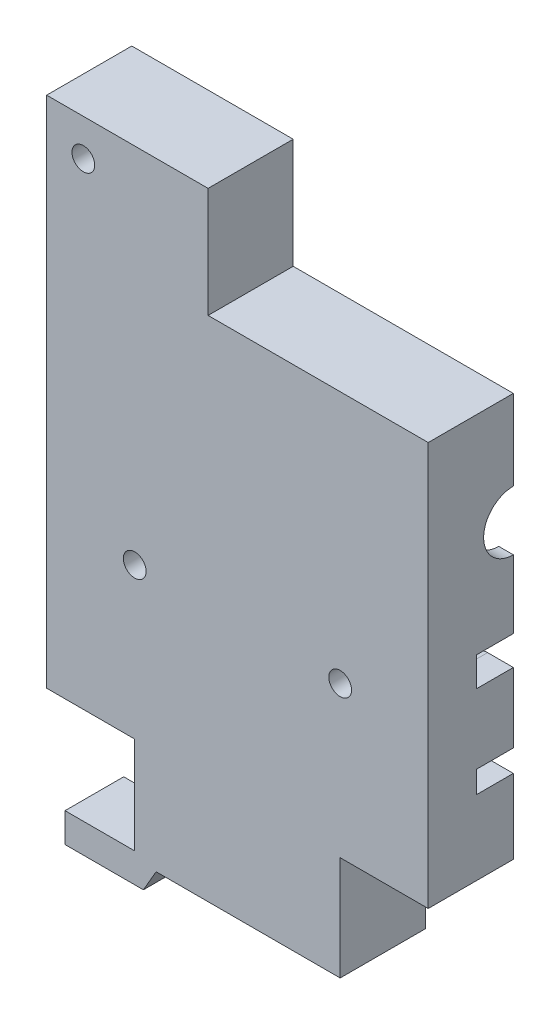
SolidWorks part; units mm, degrees
ref_plane "Alzado" through (0, 0, 0) normal (0, 0, 1) x (1, 0, 0)
ref_plane "Planta" through (0, 0, 0) normal (0, 1, 0) x (1, 0, 0)
ref_plane "Vista lateral" through (0, 0, 0) normal (1, 0, 0) x (0, 0, -1)
sketch "Croquis1" plane through (0, 0, 0) normal (0, 0, 1) x (1, 0, 0)
  line L0 (0, 0) -> (0, 90)
  line L1 (0, 90) -> (52, 90)
  line L2 (52, 90) -> (52, 0)
  line L3 (52, 0) -> (0, 0)
  dimension "D1" = 90
  dimension "D2" = 52
extrude "Saliente-Extruir1" add sketch "Croquis1" along normal blind 11.6
ref_plane "Plano1" through (50, 0, 0) normal (1, 0, 0) x (0, 0, -1)
sketch "Croquis2" plane through (50, 0, 0) normal (1, 0, 0) x (0, 0, -1)
  line L0 (0, 0) -> (0, 90) construction
  line L1 (0, 52.45) -> (0, 67.55)
  arc A0 (0, 67.55) -> (0, 52.45) centre (0, 60) ccw
  dimension "D1" = 15.1
  dimension "D2" = 30
extrude "Cortar-Extruir1" cut sketch "Croquis2" against normal blind 48
ref_plane "Plano2" through (38, 0, 0) normal (1, 0, 0) x (0, 0, -1)
sketch "Croquis3" plane through (38, 0, 0) normal (1, 0, 0) x (0, 0, -1)
  line L0 (0, 0) -> (0, 90) construction
  line L1 (0, 7.45) -> (0, 22.55)
  line L2 (-11.6, 90) -> (0, 90) construction
  arc A0 (0, 22.55) -> (0, 7.45) centre (0, 15) ccw
  dimension "D1" = 15.1
  dimension "D2" = 75
extrude "Cortar-Extruir2" cut sketch "Croquis3" against normal blind 24
sketch "Croquis4" plane through (52, 0, 0) normal (1, 0, 0) x (0, 0, -1)
  line L0 (0, 0) -> (0, 90) construction
  line L1 (0, 0) -> (0, 90)
  circle A0 centre (0, 60) radius 4.05
  dimension "D1" = 8.1
  dimension "D2" = 30
extrude "Cortar-Extruir3" cut sketch "Croquis4" against normal through all contours L1 A0 region at (52, 60, 1.7189)
sketch "Croquis5" plane through (52, 0, 0) normal (1, 0, 0) x (0, 0, -1)
  line L0 (0, 0) -> (0, 55.95) construction
  line L1 (0, 0) -> (0, 55.95)
  circle A0 centre (0, 15) radius 4.05
  dimension "D1" = 8.1
  dimension "D2" = 75
extrude "Cortar-Extruir4" cut sketch "Croquis5" against normal through all contours L1 A0 region at (52, 15, 1.7189)
sketch "Croquis6" plane through (0, 0, 0) normal (0, 0, -1) x (-1, 0, 0)
  line L10 (-2, 52.45) -> (-50, 52.45) construction
  line L13 (-2, 52.45) -> (-50, 52.45) construction
  line L18 (-2, 21.55) -> (-11.5, 21.55)
  line L19 (-11.5, 21.55) -> (-11.5, 25.05)
  line L20 (-11.5, 25.05) -> (-40.5, 25.05)
  line L21 (-2, 52.45) -> (-26, 52.45)
  line L22 (-40.5, 21.55) -> (-40.5, 25.05)
  line L23 (-40.5, 21.55) -> (-50, 21.55)
  line L24 (-26, 49.95) -> (-26, 22.55) construction
  line L25 (-2, 49.95) -> (-50, 49.95)
  line L26 (-50, 49.95) -> (-50, 21.55)
  line L27 (-2, 49.95) -> (-2, 21.55)
  line L28 (-52, 45.95) -> (-52, 48.45)
  point P1 (-6.75, 21.55)
  dimension "D2" = 9.5
  dimension "D3" = 2.5
  dimension "D4" = 9.5
  dimension "D5" = 24.9
  dimension "D6" = 28.4
  dimension "D7" = 9.5
  dimension "D8" = 3.5
  dimension "D9" = 3.5
  dimension "D10" = 9.5
extrude "Cortar-Extruir7" cut sketch "Croquis6" against normal blind 8 contours L27 L25 L26 L23 L22 L20 L19 L18 region at (26, 36.7516, 0)
sketch "Croquis7" plane through (0, 0, 8) normal (0, 0, -1) x (-1, 0, 0)
  line L0 (-2, 49.95) -> (-50, 49.95) construction
  line L3 (-50, 49.95) -> (-50, 21.55) construction
  circle A0 centre (-40, 40.55) radius 4
  dimension "D1" = 8
  dimension "D2" = 9.4
  dimension "D3" = 10
extrude "Saliente-Extruir2" add sketch "Croquis7" along normal blind 12
sketch "Croquis8" plane through (0, 0, 0) normal (0, 0, -1) x (-1, 0, 0)
  line L0 (-50, 49.95) -> (-50, 21.55) construction
  line L1 (-52, 19.05) -> (-52, 55.95) construction
  line L2 (-50, 46.65) -> (-50, 42.65)
  line L3 (-52, 42.65) -> (-52, 46.65)
  line L4 (-52, 46.65) -> (-50, 46.65)
  line L5 (-52, 42.65) -> (-50, 42.65)
  dimension "D1" = 4
  dimension "D2" = 3.3
extrude "Cortar-Extruir8" cut sketch "Croquis8" against normal blind 5
sketch "Croquis9" plane through (0, 0, 0) normal (0, 0, -1) x (-1, 0, 0)
  line L0 (-52, 42.65) -> (-48.4953, 42.65)
  line L1 (-46.4953, 40.65) -> (-46.4953, 37.65)
  line L2 (-46.4953, 37.65) -> (-52, 37.65)
  line L3 (-52, 19.05) -> (-52, 42.65) construction
  line L4 (-52, 37.65) -> (-52, 42.65)
  arc A0 (-46.4953, 40.65) -> (-48.4953, 42.65) centre (-48.4953, 40.65) ccw
  point P9 (-46.4953, 42.65)
  dimension "D3" = 2
  dimension "D1" = 5.5047
  dimension "D2" = 5
extrude "Saliente-Extruir4" add sketch "Croquis9" against normal blind 8
sketch "Croquis10" plane through (0, 0, -4) normal (0, 0, -1) x (-1, 0, 0)
  circle A0 centre (-40, 40.55) radius 4 construction
  circle A1 centre (-40, 40.55) radius 4
  circle A2 centre (-40, 40.55) radius 1.55
  dimension "D1" = 3.1
extrude "Cortar-Extruir9" cut sketch "Croquis10" against normal through all contours A2 region at (40, 40.55, -4)
sketch "Croquis11" plane through (0, 0, -4) normal (0, 0, -1) x (-1, 0, 0)
  circle A0 centre (-40, 40.55) radius 1.55 construction
  circle A1 centre (-40, 40.55) radius 1.55
  circle A2 centre (-40, 40.55) radius 2.8
  dimension "D1" = 5.6
extrude "Cortar-Extruir10" cut sketch "Croquis11" against normal blind 3
sketch "Croquis12" plane through (52, 0, 0) normal (1, 0, 0) x (0, 0, -1)
  line L0 (0, 19.05) -> (0, 42.65) construction
  line L1 (0, 30.15) -> (0, 33.15)
  line L2 (0, 33.15) -> (-5, 33.15)
  line L3 (-5, 33.15) -> (-5, 30.15)
  line L4 (-5, 30.15) -> (0, 30.15)
  dimension "D1" = 5
  dimension "D2" = 3
  dimension "D3" = 13.5
extrude "Cortar-Extruir11" cut sketch "Croquis12" against normal through all
sketch "Croquis13" plane through (0, 0, 0) normal (0, 0, -1) x (-1, 0, 0)
  line L0 (-52, 90) -> (-52, 75)
  line L2 (-52, 75) -> (-22, 75)
  line L3 (-22, 75) -> (-22, 90)
  line L4 (-52, 90) -> (0, 90) construction
  line L5 (-22, 90) -> (-52, 90)
  dimension "D1" = 30
  dimension "D2" = 15
extrude "Cortar-Extruir12" cut sketch "Croquis13" against normal blind 12
sketch "Croquis14" plane through (0, 0, 0) normal (0, 0, -1) x (-1, 0, 0)
  line L0 (-22, 90) -> (0, 90) construction
  line L1 (0, 90) -> (0, 64.05) construction
  circle A0 centre (-5, 85) radius 1.55
  circle A1 centre (-5, 85) radius 2.8
  dimension "D1" = 3.1
  dimension "D2" = 5.6
  dimension "D3" = 5
  dimension "D4" = 5
extrude "Cortar-Extruir13" cut sketch "Croquis14" against normal blind 12 contours A0 region at (5, 85, 0)
extrude "Cortar-Extruir14" cut sketch "Croquis14<3>" against normal blind 3
sketch "Croquis14<3>" plane through (0, 0, 0) normal (0, 0, -1) x (-1, 0, 0) same geometry as "Croquis14"
sketch "Croquis15" plane through (0, 0, 8) normal (0, 0, -1) x (-1, 0, 0)
  line L0 (-50, 30.15) -> (-2, 30.15)
  line L1 (-2, 30.15) -> (-2, 28.95)
  line L2 (-2, 30.15) -> (-2, 21.55) construction
  line L3 (-2, 28.95) -> (-50, 28.95)
  line L4 (-50, 30.15) -> (-50, 21.55) construction
  line L5 (-50, 28.95) -> (-50, 30.15)
  dimension "D1" = 1.2
extrude "Saliente-Extruir5" add sketch "Croquis15" along normal blind 8
sketch "Croquis16" plane through (0, 0, 0) normal (0, 0, -1) x (-1, 0, 0)
  line L0 (-52, 20) -> (-52, 0)
  line L2 (-52, 0) -> (-40, 0)
  line L3 (0, 0) -> (-52, 0) construction
  line L4 (-40, 0) -> (-40, 20)
  line L5 (-40, 20) -> (-52, 20)
  dimension "D1" = 20
  dimension "D2" = 12
extrude "Cortar-Extruir15" cut sketch "Croquis16" against normal through all
sketch "Croquis17" plane through (0, 0, 0) normal (0, 0, -1) x (-1, 0, 0)
  line L0 (0, 20) -> (-12, 20)
  line L1 (-12, 20) -> (-12, 0)
  line L2 (0, 0) -> (-40, 0) construction
  line L3 (-12, 0) -> (0, 0)
  line L4 (0, 0) -> (0, 20)
  dimension "D1" = 12
  dimension "D2" = 20
  dimension "D3" = 10.15
extrude "Cortar-Extruir16" cut sketch "Croquis17" against normal through all
sketch "Croquis18" plane through (0, 0, 11.6) normal (0, 0, 1) x (1, 0, 0)
  line L0 (2.5, 2.8) -> (12, 2.8)
  line L2 (2.5, 2.8) -> (2.5, 6.8)
  line L3 (2.5, 6.8) -> (12, 6.8)
  line L4 (12, 20) -> (12, 0) construction
  line L5 (12, 6.8) -> (12, 2.8)
  dimension "D1" = 4
  dimension "D2" = 2.8
  dimension "D3" = 9.5
extrude "Saliente-Extruir6" add sketch "Croquis18" against normal blind 8
sketch "Croquis19" plane through (0, 0, 8) normal (0, 0, -1) x (-1, 0, 0)
  line L0 (-2, 49.95) -> (-2, 33.15) construction
  line L1 (-2, 49.95) -> (-50, 49.95) construction
  circle A0 centre (-12, 40.55) radius 4
  dimension "D1" = 8
  dimension "D2" = 10
  dimension "D3" = 9.4
extrude "Saliente-Extruir7" add sketch "Croquis19" along normal up to surface (12 mm away) up to face at (37.2, 40.55, -4)
sketch "Croquis20" plane through (0, 0, -4) normal (0, 0, -1) x (-1, 0, 0)
  circle A0 centre (-12, 40.55) radius 4 construction
  circle A1 centre (-12, 40.55) radius 4
  circle A2 centre (-12, 40.55) radius 1.55
  circle A3 centre (-12, 40.55) radius 2.8
  dimension "D1" = 3.1
  dimension "D2" = 5.6
extrude "Cortar-Extruir17" cut sketch "Croquis20" against normal through all contours A2 region at (12, 40.55, -4)
extrude "Cortar-Extruir18" cut sketch "Croquis20<3>" against normal blind 3 contours A3 A2 region at (14.7208, 40.55, -4)
sketch "Croquis20<3>" plane through (0, 0, -4) normal (0, 0, -1) x (-1, 0, 0) same geometry as "Croquis20"
sketch "Croquis21" plane through (0, 0, 11.6) normal (0, 0, 1) x (1, 0, 0)
  line L0 (12, 2.8) -> (40, 2.8)
  line L1 (40, 0) -> (40, 20) construction
  line L2 (40, 2.8) -> (40, 0)
  line L3 (40, 0) -> (12, 0)
  line L4 (12, 2.8) -> (12, 0) construction
  line L5 (12, 0) -> (40, 0) construction
  line L6 (12, 0) -> (12, 2.8)
extrude "Cortar-Extruir19" cut sketch "Croquis21" against normal through all
sketch "Croquis22" plane through (0, 0, 11.6) normal (0, 0, 1) x (1, 0, 0)
  line L0 (2.5, 2.8) -> (40, 2.8) construction
  line L1 (13.1845, 2.8) -> (40, 2.8)
  line L2 (13.1845, 2.8) -> (14.9166, 5.8)
  line L3 (14.9166, 5.8) -> (40, 5.8)
  line L4 (40, 2.8) -> (40, 20) construction
  line L5 (40, 2.8) -> (40, 5.8)
  dimension "D1" = 25.0834
  dimension "D3" = 60
  dimension "D4" = 10.6845
extrude "Cortar-Extruir20" cut sketch "Croquis22" against normal through all
